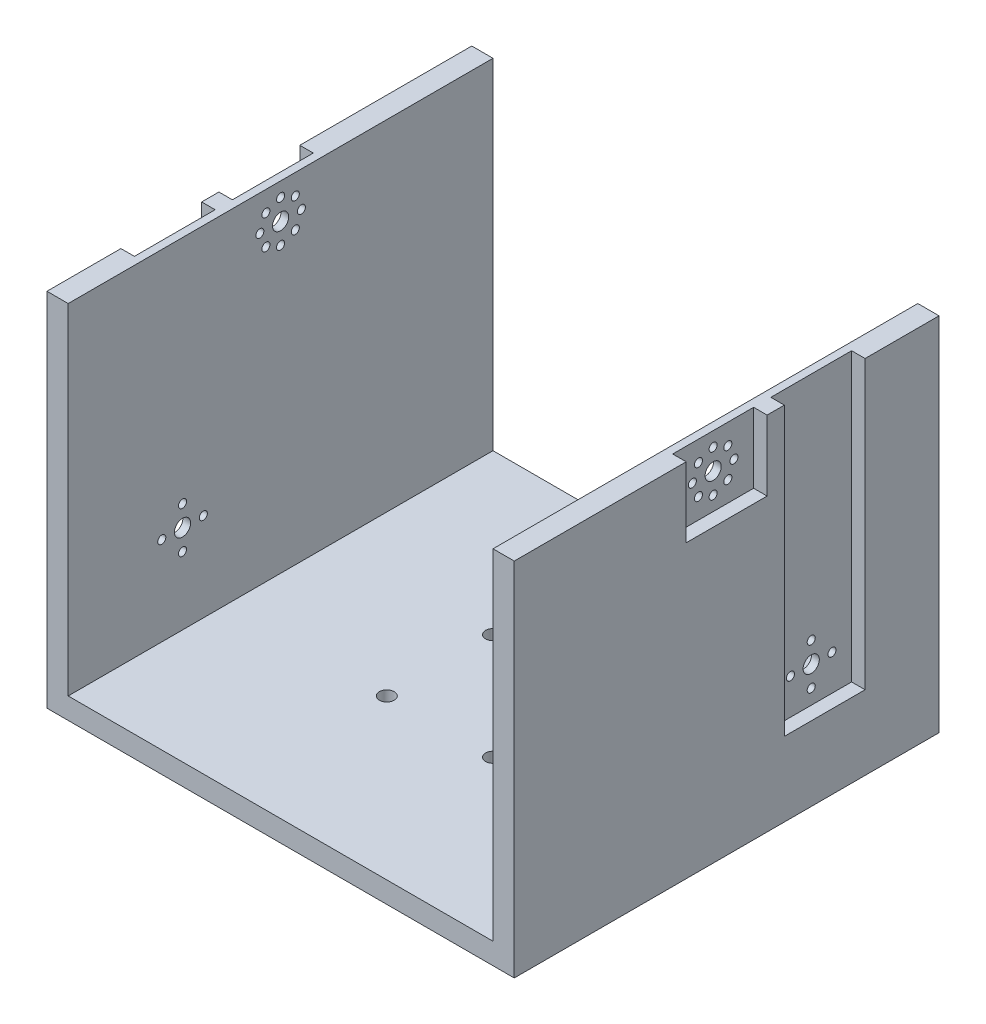
SolidWorks part; units mm, degrees
ref_plane "Front" through (0, 0, 0) normal (0, 0, 1) x (1, 0, 0)
ref_plane "Top" through (0, 0, 0) normal (0, 1, 0) x (1, 0, 0)
ref_plane "Right" through (0, 0, 0) normal (1, 0, 0) x (0, 0, -1)
sketch "Sketch2" plane through (0, 0, 0) normal (0, 1, 0) x (1, 0, 0)
  line L0 (0, 0) -> (0, -100) construction
  line L1 (-100, -100) -> (100, -100)
  line L2 (-100, -100) -> (-100, 100)
  line L3 (-100, 100) -> (100, 100)
  line L4 (100, -100) -> (100, 100)
  line L5 (0, 0) -> (-100, 0) construction
  point P0 (0, 0)
  dimension "D1" = 200
  dimension "D2" = 200
extrude "Boss-Extrude1" add sketch "Sketch2" along normal blind 10
sketch "Sketch3" plane through (0, 0, 0) normal (0, 1, 0) x (1, 0, 0)
  line L0 (-100, -100) -> (100, -100) construction
  line L1 (-100, 100) -> (-110, 100)
  line L2 (-100, 100) -> (-100, -100)
  line L3 (-100, -100) -> (-110, -100)
  line L4 (-110, 100) -> (-110, -100)
  line L5 (0, 0) -> (0, 100) construction
  line L6 (100, 100) -> (-100, 100) construction
  line L7 (110, 100) -> (110, -100)
  line L8 (100, -100) -> (110, -100)
  line L9 (100, 100) -> (100, -100)
  line L10 (100, 100) -> (110, 100)
  dimension "D1" = 10
extrude "Boss-Extrude2" add sketch "Sketch3" along normal blind 170
sketch "Sketch4" plane through (0, 10, 0) normal (0, 1, 0) x (1, 0, 0)
  point P4 (0, 0)
hole_wizard "M6 Clearance Hole1" positions "Sketch5" profile "Sketch6" hole size "M6" standard "ANSI Metric" end condition up to next
sketch "Sketch5" plane through (0, 10, 0) normal (0, 1, 0) x (1, 0, 0)
  line L0 (0, 0) -> (0, 25) construction
  line L1 (0, 25) -> (-25, 25) construction
  line L3 (0, 25) -> (25, 25) construction
  point P0 (-25, 25)
  point P13 (25, 25)
  point P14 (25, -25)
  point P15 (-25, -25)
  dimension "D1" = 25
  dimension "D2" = 4
sketch "Sketch6" plane through (-25, 10, -25) normal (1, 0, 0) x (0, 0, 1)
  line L0 (0, 0) -> (0, 10)
  line L1 (0, 10) -> (3.5, 10)
  line L2 (3.5, 10) -> (3.5, 0)
  line L5 (3.5, 0) -> (0, 0)
  line L11 (0, -6.35) -> (0, 107.95) construction
  dimension "Thru Hole Dia." = 7
  dimension "Thru Hole Depth" = 10
sketch "Sketch7" plane through (100, 0, 0) normal (-1, 0, 0) x (0, 0, 1)
  line L0 (-100, 170) -> (100, 170) construction
  line L1 (0, 153.49) -> (0, 163.269) construction
  line L2 (0, 153.49) -> (0, 163.269) construction
  circle A0 centre (0, 153.49) radius 3.81
  circle A1 centre (0, 163.269) radius 1.8987
  circle A2 centre (6.9148, 160.4048) radius 1.8987
  circle A3 centre (9.779, 153.49) radius 1.8987
  circle A4 centre (6.9148, 146.5752) radius 1.8987
  circle A5 centre (0, 143.711) radius 1.8987
  circle A6 centre (-6.9148, 146.5752) radius 1.8987
  circle A7 centre (-9.779, 153.49) radius 1.8987
  circle A8 centre (-6.9148, 160.4048) radius 1.8987
  point P7 (0, 170)
  dimension "D1" = 7.62
  dimension "D3" = 3.7973
  dimension "D2" = 16.51
  dimension "D6" = 9.779
  dimension "D5" = 8
extrude "Cut-Extrude1" cut sketch "Sketch7" against normal through all both and the other way through all
sketch "Sketch8" plane through (0, 170, 0) normal (0, 1, 0) x (1, 0, 0)
  line L1 (103.65, -19.05) -> (110, -19.05)
  line L2 (103.65, -19.05) -> (103.65, 19.05)
  line L3 (103.65, 19.05) -> (110, 19.05)
  line L4 (110, -19.05) -> (110, 19.05)
  line L5 (103.65, -19.05) -> (110, 19.05) construction
  line L6 (103.65, 19.05) -> (110, -19.05) construction
  line L9 (110, -100) -> (110, 100) construction
  line L10 (0, 0) -> (0, 100) construction
  line L11 (100, 100) -> (-100, 100) construction
  line L13 (-103.65, 19.05) -> (-110, -19.05) construction
  line L14 (-103.65, -19.05) -> (-110, 19.05) construction
  line L16 (-110, -19.05) -> (-110, 19.05)
  line L17 (-103.65, 19.05) -> (-110, 19.05)
  line L18 (-103.65, -19.05) -> (-103.65, 19.05)
  line L19 (-103.65, -19.05) -> (-110, -19.05)
  point P0 (106.825, 0)
  point P12 (110, 0)
  point P23 (-106.825, 0)
  dimension "D1" = 38.1
  dimension "D2" = 6.35
extrude "Cut-Extrude2" cut sketch "Sketch8" against normal blind 33.02
sketch "Sketch9" plane through (110, 0, 0) normal (1, 0, 0) x (0, 0, -1)
  line L0 (29.6609, 34.949) -> (35.7569, 34.949) construction
  line L2 (65.1809, 68.487) -> (65.1809, 34.939)
  line L3 (65.1809, 34.939) -> (27.1609, 34.939)
  line L4 (27.1609, 68.487) -> (27.1609, 34.939)
  line L5 (65.1809, 68.487) -> (27.1609, 34.939) construction
  line L6 (65.1809, 34.939) -> (27.1609, 68.487) construction
  line L7 (29.6609, 44.093) -> (29.6609, 34.949) construction
  line L13 (65.1809, 68.487) -> (65.1809, 170)
  line L14 (19.05, 170) -> (100, 170) construction
  line L15 (65.1809, 170) -> (27.1609, 170)
  line L16 (27.1609, 170) -> (27.1609, 68.487)
  point P0 (46.1709, 51.713)
  point P10 (46.1709, 61.492)
  point P11 (36.3919, 51.713)
  point P13 (46.1709, 41.934)
  point P15 (55.9499, 51.713)
  dimension "D1" = 0.01
  dimension "D2" = 2.5
extrude "Cut-Extrude3" cut sketch "Sketch9" against normal blind 6.35
sketch "Sketch11" plane through (103.65, 0, 0) normal (1, 0, 0) x (0, 0, -1)
  circle A0 centre (46.1709, 51.713) radius 3.81
  circle A1 centre (0, 153.49) radius 3.81 construction
extrude "Cut-Extrude4" cut sketch "Sketch11" against normal up to next
hole_wizard "#6 Clearance Hole1" positions "Sketch12" profile "Sketch13" hole size "#6" standard "ANSI Inch" end condition up to next
sketch "Sketch12" plane through (103.65, 0, 0) normal (1, 0, 0) x (0, 0, -1)
  point P0 (46.1709, 61.492)
  point P3 (36.3919, 51.713)
  point P6 (55.9499, 51.713)
  point P10 (46.1709, 41.934)
sketch "Sketch13" plane through (103.65, 61.492, -46.1709) normal (0, 1, 0) x (0, 0, -1)
  line L0 (0, 0) -> (0, 3.65)
  line L1 (0, 3.65) -> (1.8986, 3.65)
  line L2 (1.8986, 3.65) -> (1.8986, 0)
  line L5 (1.8986, 0) -> (0, 0)
  line L11 (0, -6.35) -> (0, 107.95) construction
  dimension "Thru Hole Dia." = 3.7973
  dimension "Thru Hole Depth" = 3.65
ref_plane "Plane1" through (0, 0, 0) normal (-0.7071, 0, 0.7071) x (0.7071, 0, 0.7071)
ref_axis "Axis1" through (0, 0, 0) along (0, 1, 0)
pattern_circular "CirPattern1" count 2 over 360 about axis through (0, 0, 0) along (0, 1, 0) of "Cut-Extrude3", "Cut-Extrude4", "#6 Clearance Hole1"
equation "\"Longueur\"= 200"
equation "\"D2@Sketch2\"=\"Longueur\""
equation "\"Largeur\"=200"
equation "\"D1@Sketch2\"=\"Largeur\""
